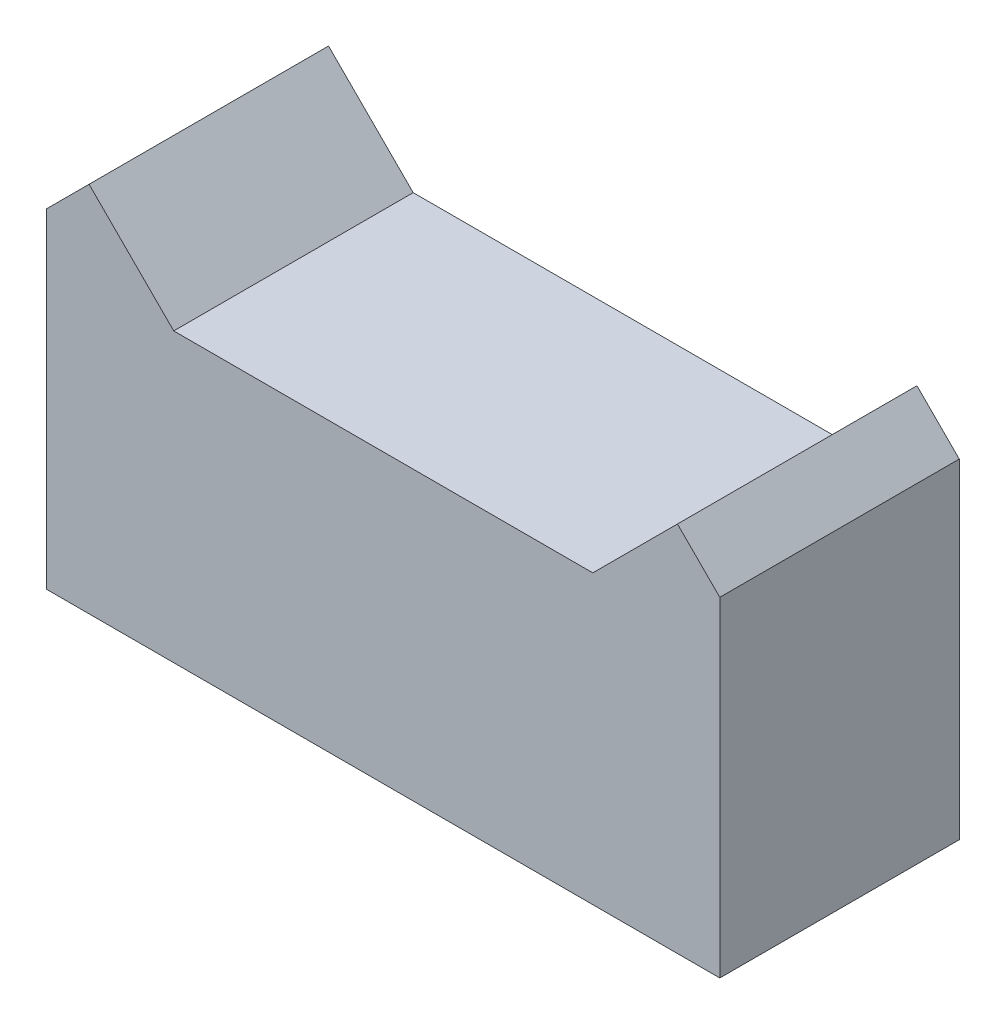
SolidWorks part; units mm, degrees
material "6061 Alloy"
ref_plane "Front Plane" through (0, 0, 0) normal (0, 0, 1) x (1, 0, 0)
ref_plane "Top Plane" through (0, 0, 0) normal (0, 1, 0) x (1, 0, 0)
ref_plane "Right Plane" through (0, 0, 0) normal (1, 0, 0) x (0, 0, -1)
sketch "Sketch2" plane through (0, 0, 0) normal (0, 0, 1) x (1, 0, 0)
  line L0 (0, 0) -> (0, -21)
  line L1 (0, -21) -> (17.5, -21)
  line L2 (17.5, -21) -> (24.5711, -13.9289)
  line L3 (0, -21) -> (-17.5, -21)
  line L4 (-17.5, -21) -> (-24.5711, -13.9289)
  line L5 (0, -21) -> (0, -45)
  line L6 (-17.5, -21) -> (-17.5, -45)
  line L7 (-17.5, -45) -> (0, -45)
  line L8 (0, -45) -> (17.5, -45)
  line L9 (17.5, -45) -> (17.5, -21)
  line L10 (-24.5711, -13.9289) -> (-28.1066, -17.4645)
  line L11 (-28.1066, -17.4645) -> (-28.1066, -45)
  line L12 (-28.1066, -45) -> (-17.5, -45)
  line L13 (24.5711, -13.9289) -> (28.1066, -17.4645)
  line L14 (28.1066, -17.4645) -> (28.1066, -45)
  line L15 (28.1066, -45) -> (17.5, -45)
  dimension "D1" = 21
  dimension "D2" = 17.5
  dimension "D3" = 10
  dimension "D4" = 135
  dimension "D5" = 17.5
  dimension "D6" = 10
  dimension "D7" = 135
  dimension "D8" = 24
  dimension "D9" = 27.5355
  dimension "D10" = 27.5355
  dimension "D11" = 5
extrude "Boss-Extrude1" add sketch "Sketch2" along normal blind 10 and the other way blind 10 contours L8 L9 L1 L5 | L6 L7 L5 L3 | L15 L14 L13 L2 L9 | L11 L12 L6 L4 L10 region at (-8.75, -33, 0) region at (8.75, -33, 0) region at (22.9638, -30.8697, 0) region at (-22.9638, -30.8697, 0)
sketch "Sketch3" plane through (0, 0, -10) normal (0, 0, -1) x (-1, 0, 0)
  line L0 (0, 0) -> (0, -45)
  line L1 (28.1066, -45) -> (-28.1066, -45) construction
  line L2 (0, -45) -> (0, -33)
  line L3 (0, -33) -> (10, -33)
  line L4 (10, -33) -> (10, -36)
  line L5 (10, -36) -> (0, -36)
  line L6 (0, -36) -> (-9.9848, -36)
  line L7 (-9.9848, -36) -> (-9.9848, -33)
  line L8 (-9.9848, -33) -> (0, -33)
  line L9 (17.5, -21) -> (-17.5, -21) construction
  dimension "D1" = 3
  dimension "D2" = 10
  dimension "D3" = 9.9848
  dimension "D4" = 15
extrude "Cut-Extrude1" cut sketch "Sketch3" against normal blind 10 contours L8 L7 L6 L0 | L5 L4 L3 L0 region at (-5, -34.5, -10) region at (4.9924, -34.5, -10)
